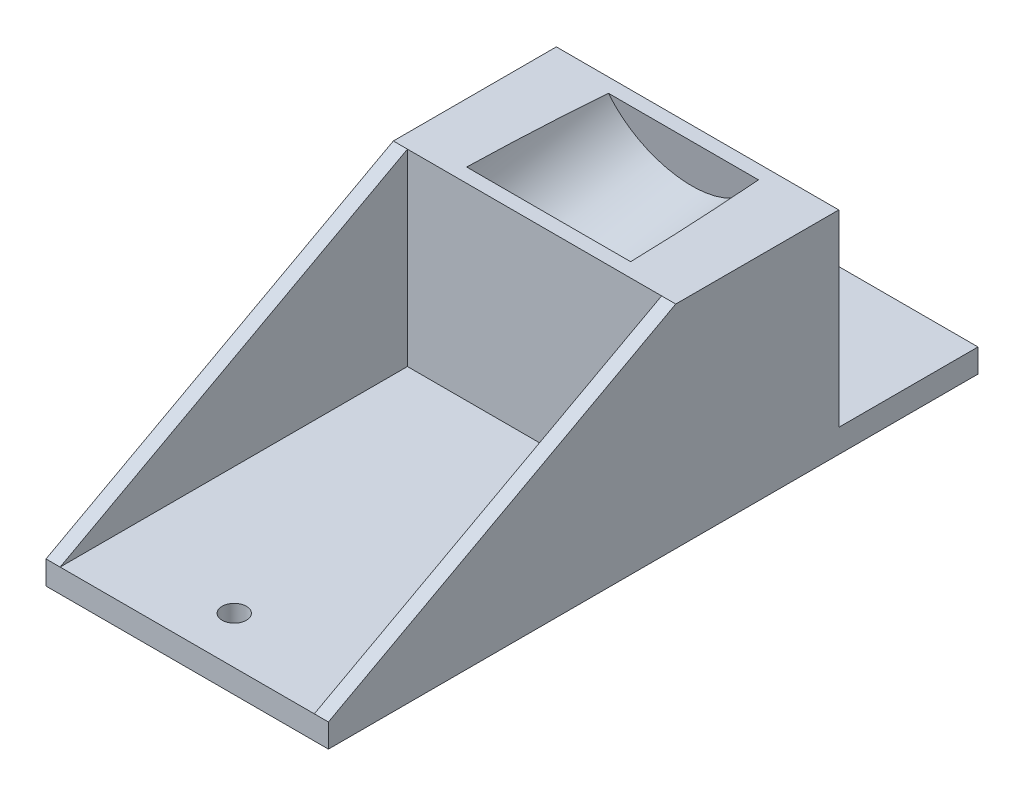
SolidWorks part; units mm, degrees
ref_plane "Front Plane" through (0, 0, 0) normal (0, 0, 1) x (1, 0, 0)
ref_plane "Top Plane" through (0, 0, 0) normal (0, 1, 0) x (1, 0, 0)
ref_plane "Right Plane" through (0, 0, 0) normal (1, 0, 0) x (0, 0, -1)
ref_plane "Plane4" through (0, 474.726, 0) normal (0, 1, 0) x (1, 0, 0)
sketch "Sketch7" plane through (0, 474.726, 0) normal (0, 1, 0) x (1, 0, 0)
  line L0 (444.5, -678.561) -> (-444.5, -678.561) construction
  line L1 (-38.1, -564.261) -> (38.1, -564.261)
  line L2 (-38.1, -564.261) -> (-38.1, -653.161)
  line L3 (-38.1, -653.161) -> (38.1, -653.161)
  line L4 (38.1, -564.261) -> (38.1, -653.161)
  line L6 (444.5, -678.561) -> (-444.5, -678.561) construction
  point P6 (0, -653.161)
  point P9 (0, -678.561)
  dimension "D1" = 88.9
  dimension "D2" = 76.2
  dimension "D3" = 25.4
extrude "Boss-Extrude1" add sketch "Sketch7" along normal blind 57.15
sketch "Sketch8" plane through (0, -83.6446, 474.3722) normal (0, 0.1736, -0.9848) x (-1, 0, 0)
  circle A0 centre (0, 634.5034) radius 22.225 construction
  circle A1 centre (0, 634.5034) radius 22.225 construction
  circle A2 centre (0, 634.5034) radius 22.352
  dimension "D1" = 0.127
extrude "Boss-Extrude2" add sketch "Sketch8" against normal blind 35.687 and the other way blind 0.127 separate body
combine bodies "Combine1" operation type subtract main body 102 bodies to subtract 103
sketch "Sketch10" plane through (38.1, 0, 0) normal (1, 0, 0) x (0, 0, -1)
  line L1 (-582.7761, 531.876) -> (-619.1426, 531.876) construction
  line L2 (-653.161, 474.726) -> (-653.161, 481.076)
  line L3 (-653.161, 481.076) -> (-622.9526, 481.076)
  line L4 (-653.161, 474.726) -> (-564.261, 474.726)
  line L5 (-564.261, 474.726) -> (-564.261, 531.876)
  line L6 (-564.261, 531.876) -> (-653.161, 531.876)
  line L7 (-653.161, 531.876) -> (-653.161, 474.726)
  line L8 (-653.161, 474.726) -> (-564.261, 474.726) construction
  line L9 (-564.261, 474.726) -> (-564.261, 531.876) construction
  line L10 (-564.261, 531.876) -> (-653.161, 531.876) construction
  line L11 (-653.161, 531.876) -> (-653.161, 474.726) construction
  line L12 (-622.9526, 481.076) -> (-622.9526, 531.876)
  line L13 (-622.9526, 531.876) -> (-653.161, 531.876)
  line L14 (-653.161, 531.876) -> (-653.161, 481.076)
  line L15 (-653.161, 474.726) -> (-564.261, 474.726) construction
  line L16 (-564.261, 531.876) -> (-578.9661, 531.876)
  line L17 (-564.261, 531.876) -> (-564.261, 481.076)
  line L18 (-564.261, 481.076) -> (-578.9661, 481.076)
  line L19 (-578.9661, 531.876) -> (-578.9661, 481.076)
  point P14 (-619.1426, 531.876)
  point P16 (0, 0)
  point P17 (-582.8899, 531.876)
  point P20 (0, 0)
  point P21 (0, 0)
  line M11 (-564.261, 474.726) -> (-564.261, 531.876)
  line M12 (-564.261, 531.876) -> (-653.161, 531.876)
  line M13 (-653.161, 531.876) -> (-653.161, 474.726)
  dimension "D2" = 3.81
  dimension "D3" = 6.35
  dimension "D4" = 3.81
  dimension "D5" = 6.35
  dimension "D1" = 0
extrude "Cut-Extrude2" cut sketch "Sketch10" against normal through all contours L3 L12 M12 M13 | L19 L18 M12 M11 region at (38.1, 506.476, 638.0568) region at (38.1, 506.476, 571.6136)
sketch "Sketch11" plane through (0, 0, 564.261) normal (0, 0, -1) x (-1, 0, 0)
  line L4 (38.1, 481.076) -> (-38.1, 481.076)
  line L5 (-38.1, 481.076) -> (-38.1, 474.726)
  line L6 (-38.1, 474.726) -> (38.1, 474.726)
  line L7 (38.1, 474.726) -> (38.1, 481.076)
  line L8 (38.1, 481.076) -> (-38.1, 481.076)
  line L9 (-38.1, 481.076) -> (-38.1, 474.726)
  line L10 (-38.1, 474.726) -> (38.1, 474.726)
  line L11 (38.1, 474.726) -> (38.1, 481.076)
  dimension "D1" = 0
extrude "Boss-Extrude3" add sketch "Sketch11" along normal blind 22.86 contours L8 L9 L10 L11
sketch "Sketch14" plane through (0, 0, 653.161) normal (0, 0, 1) x (1, 0, 0)
  line L4 (38.1, 474.726) -> (38.1, 481.076)
  line L5 (38.1, 481.076) -> (-38.1, 481.076)
  line L6 (-38.1, 481.076) -> (-38.1, 474.726)
  line L7 (-38.1, 474.726) -> (38.1, 474.726)
  line L8 (38.1, 474.726) -> (38.1, 481.076)
  line L9 (38.1, 481.076) -> (-38.1, 481.076)
  line L10 (-38.1, 481.076) -> (-38.1, 474.726)
  line L11 (-38.1, 474.726) -> (38.1, 474.726)
  dimension "D1" = 0
extrude "Boss-Extrude4" add sketch "Sketch14" along normal blind 63.5
sketch "Sketch12" plane through (0, 474.726, 0) normal (0, -1, 0) x (1, 0, 0)
  circle A0 centre (0, 703.961) radius 3.2766
  circle A1 centre (0, 551.561) radius 3.2766
  point P4 (0, 0)
  point P8 (0, 551.561)
  point P10 (0, 703.961)
  dimension "D1" = 6.5532
extrude "Cut-Extrude3" cut sketch "Sketch12" against normal through all
sketch "Sketch17" plane through (38.1, 0, 0) normal (1, 0, 0) x (0, 0, -1)
  line L0 (-716.661, 481.076) -> (-622.9526, 531.876)
rib "Rib5" sketch "Sketch17" sketch "Sketch17" thickness 3.81 extrusion direction parallel to sketch draft on no parameters "D1"=3.81
mirror "Mirror1" about plane through (0, 0, 0) normal (1, 0, 0) of "Rib5"
